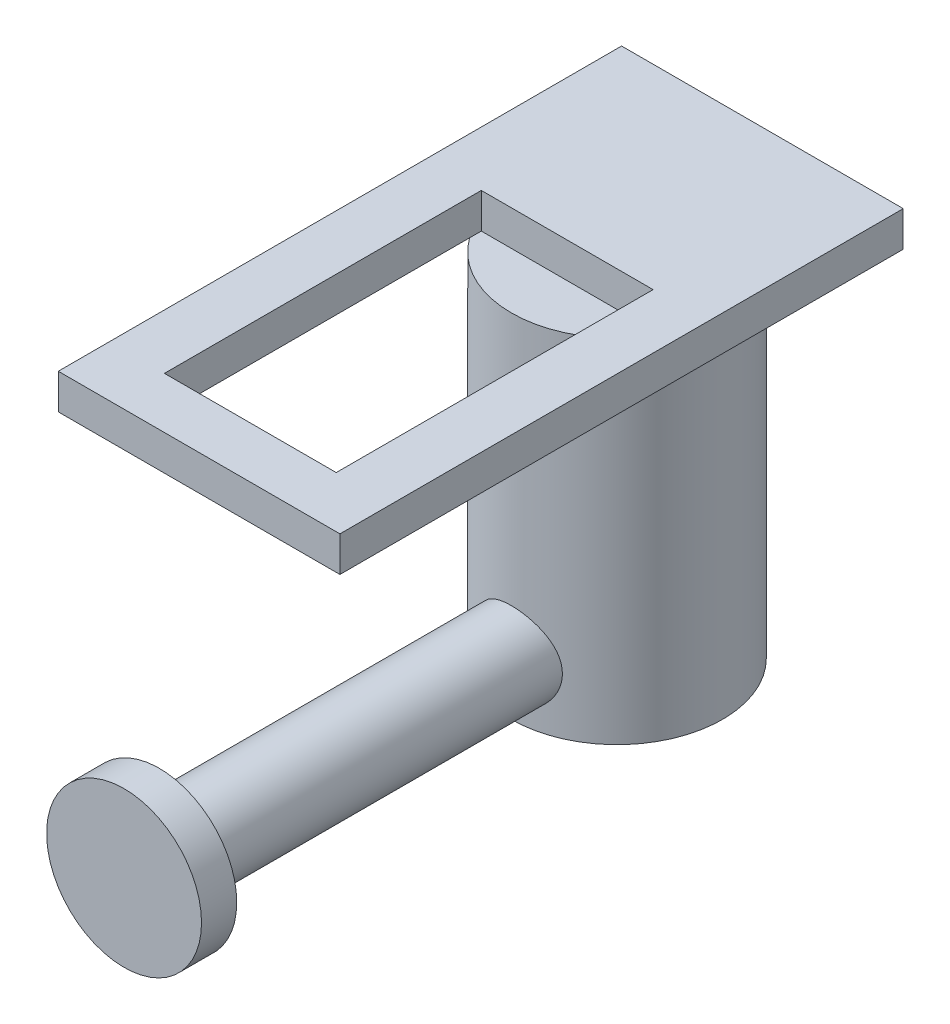
SolidWorks part; units mm, degrees
ref_plane "Front Plane" through (0, 0, 0) normal (0, 0, 1) x (1, 0, 0)
ref_plane "Top Plane" through (0, 0, 0) normal (0, 1, 0) x (1, 0, 0)
ref_plane "Right Plane" through (0, 0, 0) normal (1, 0, 0) x (0, 0, -1)
sketch "Sketch1" plane through (0, 0, 0) normal (0, 1, 0) x (1, 0, 0)
  circle A0 centre (0, 0) radius 15
  dimension "D1" = 30
extrude "Boss-Extrude1" add sketch "Sketch1" along normal blind 50
ref_plane "Plane1" through (0, 0, 15) normal (0, 0, 1) x (1, 0, 0)
sketch "Sketch2" plane through (0, 0, 15) normal (0, 0, 1) x (1, 0, 0)
  circle A0 centre (0, 8) radius 6
  dimension "D1" = 12
  dimension "D2" = 8
extrude "Boss-Extrude2" add sketch "Sketch2" along normal blind 50 and the other way up to surface separate body other way up to face at (0, 50, 15)
sketch "Sketch6" plane through (0, 0, 65) normal (0, 0, 1) x (1, 0, 0)
  circle A0 centre (0, 8) radius 11
  dimension "D1" = 22
extrude "Boss-Extrude4" add sketch "Sketch6" along normal blind 5
sketch "Sketch7" plane through (0, 50, 0) normal (0, 1, 0) x (1, 0, 0)
  line L1 (-20, -59.3447) -> (20, -59.3447)
  line L2 (-20, -59.3447) -> (-20, 20.6553)
  line L3 (-20, 20.6553) -> (20, 20.6553)
  line L4 (20, -59.3447) -> (20, 20.6553)
  line L5 (-12.2, -52.068) -> (12.2, -52.068)
  line L6 (-12.2, -52.068) -> (-12.2, -7.068)
  line L7 (-12.2, -7.068) -> (12.2, -7.068)
  line L8 (12.2, -52.068) -> (12.2, -7.068)
  point P7 (0, -52.068)
  point P10 (0, -59.3447)
  dimension "D1" = 20
  dimension "D2" = 40
  dimension "D3" = 80
  dimension "D4" = 45
  dimension "D5" = 24.4
extrude "Boss-Extrude5" add sketch "Sketch7" along normal blind 5
